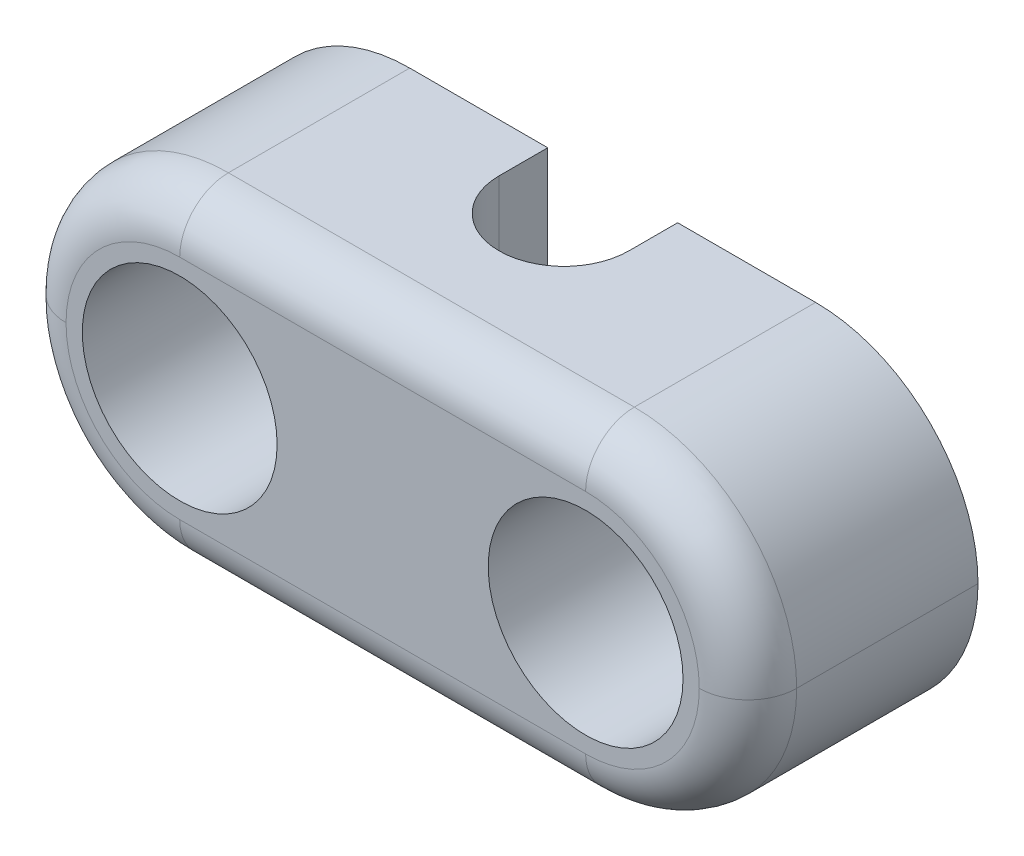
SolidWorks part; units mm, degrees
material "Plain Carbon Steel"
ref_plane "Front Plane" through (0, 0, 0) normal (0, 0, 1) x (1, 0, 0)
ref_plane "Top Plane" through (0, 0, 0) normal (0, 1, 0) x (1, 0, 0)
ref_plane "Right Plane" through (0, 0, 0) normal (1, 0, 0) x (0, 0, -1)
sketch "Sketch2" plane through (0, 0, 0) normal (0, 0, 1) x (1, 0, 0)
  line L1 (-22.5, -10) -> (22.5, -10)
  line L2 (-22.5, -10) -> (-22.5, 10)
  line L3 (-22.5, 10) -> (22.5, 10)
  line L4 (22.5, -10) -> (22.5, 10)
  line L5 (-22.5, -10) -> (22.5, 10) construction
  line L6 (-22.5, 10) -> (22.5, -10) construction
  point P0 (0, 0)
  dimension "D1" = 45
  dimension "D2" = 20
extrude "Boss-Extrude2" add sketch "Sketch2" along normal blind 14.1679
fillet "Fillet1" radius 10 4 edges at (22.5, 10, 7.0839) (22.5, -10, 7.0839) (-22.5, 10, 7.0839) (-22.5, -10, 7.0839)
sketch "Sketch3" plane through (0, -10, 0) normal (0, -1, 0) x (1, 0, 0)
  line L0 (0, 0) -> (0, 3) construction
  line L1 (-12.5, 0) -> (12.5, 0) construction
  line L2 (-4, 0) -> (-4, 3)
  line L3 (4, 0) -> (4, 3)
  line L5 (-12.5, 14.1679) -> (12.5, 14.1679) construction
  arc A0 (-4, 0) -> (4, 0) centre (0, 0) ccw
  arc A1 (4, 3) -> (-4, 3) centre (0, 3) ccw
  point P4 (0, 1.5)
  dimension "D2" = 7
  dimension "D3" = 7.1679
  dimension "D1" = 8
extrude "Cut-Extrude1" cut sketch "Sketch3" against normal blind 22
hole_wizard "CBORE for M5 Hex Head Bolt1" positions "Sketch8" profile "Sketch7" counterbore size "M5" standard "ANSI Metric" end condition through all
sketch "Sketch8" plane through (0, 0, 14.1679) normal (0, 0, 1) x (1, 0, 0)
  point P0 (-12.5, 0)
  point P2 (12.5, 0)
  dimension "D1" = 25
  dimension "D2" = 10
  dimension "D3" = 10
sketch "Sketch7" plane through (-12.5, 0, 14.1679) normal (1, 0, 0) x (0, -1, 0)
  line L0 (0, 0) -> (0, 14.1679)
  line L1 (0, 14.1679) -> (2.75, 14.1679)
  line L3 (2.75, 14.1679) -> (2.75, 10)
  line L4 (2.75, 10) -> (6, 10)
  line L5 (6, 10) -> (6, 0)
  line L7 (6, 0) -> (0, 0)
  line L11 (0, -6.35) -> (0, 107.95) construction
  dimension "Thru Hole Dia." = 5.5
  dimension "Thru Hole Depth" = 14.1679
  dimension "C'Bore Dia." = 12
  dimension "C'Bore Depth" = 10
fillet "Fillet2" radius 3 6 edges at (-19.5711, -7.0711, 14.1679) (-19.5711, 7.0711, 14.1679) (0, 10, 14.1679) (19.5711, 7.0711, 14.1679) (19.5711, -7.0711, 14.1679) (0, -10, 14.1679)
